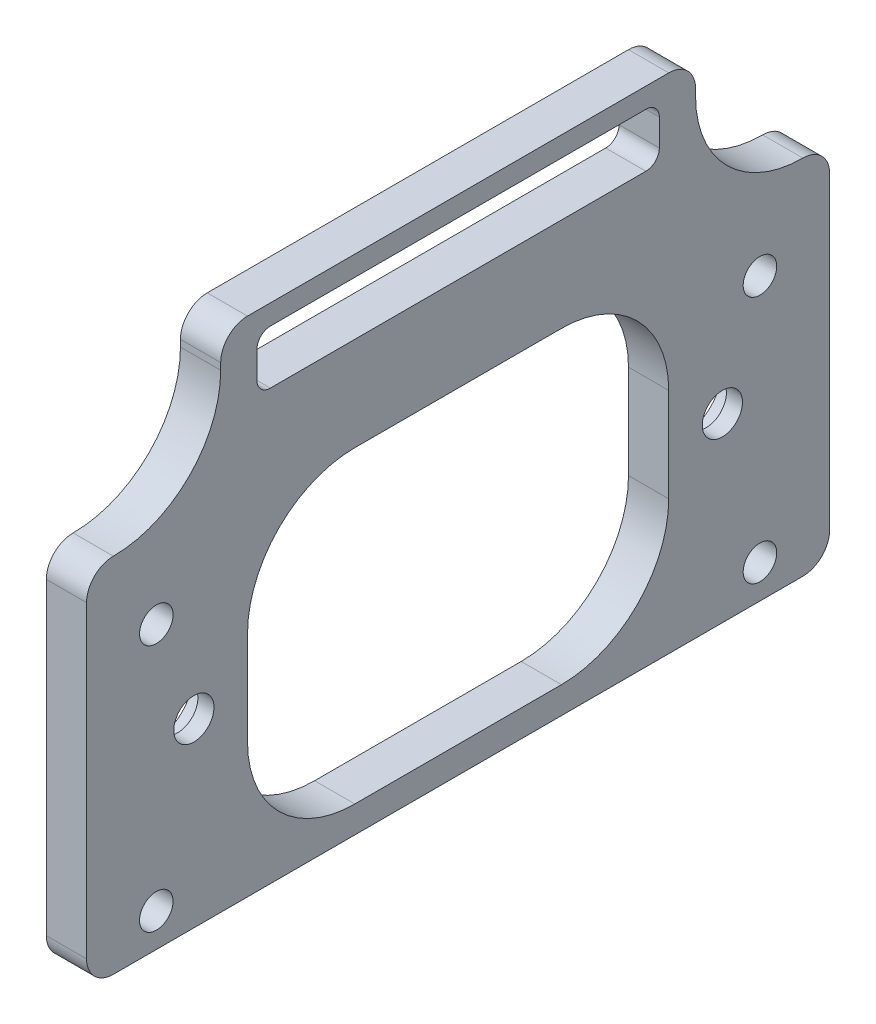
SolidWorks part; units mm, degrees
material "3.0205 (EN-AW 1200)"
ref_plane "前视基准面" through (0, 0, 0) normal (0, 0, 1) x (1, 0, 0)
ref_plane "上视基准面" through (0, 0, 0) normal (0, 1, 0) x (1, 0, 0)
ref_plane "右视基准面" through (0, 0, 0) normal (1, 0, 0) x (0, 0, -1)
other "Configuration Table"
sketch "草图1" plane through (0, 0, 0) normal (1, 0, 0) x (0, 0, -1)
  line L1 (0, 0) -> (55.4, 0)
  line L2 (0, 0) -> (0, 37.5)
  line L3 (0, 37.5) -> (55.4, 37.5)
  line L4 (55.4, 0) -> (55.4, 37.5)
  line L5 (12.7, 36) -> (42.7, 36)
  line L6 (12.7, 36) -> (12.7, 32)
  line L7 (12.7, 32) -> (42.7, 32)
  line L8 (42.7, 36) -> (42.7, 32)
  dimension "D1" = 55.4
  dimension "D2" = 37.5
  dimension "D3" = 1.5
  dimension "D4" = 12.7
  dimension "D5" = 30
  dimension "D6" = 4
extrude "凸台-拉伸1" add sketch "草图1" along normal blind 3
sketch "草图2" plane through (3, 0, 0) normal (1, 0, 0) x (0, 0, -1)
  line L0 (0, 37.5) -> (0, 0) construction
  line L1 (0, 0) -> (55.4, 0) construction
  circle A0 centre (5.2, 21) radius 1.25
  circle A1 centre (5.2, 2.5) radius 1.25
  circle A2 centre (50.2, 21) radius 1.25
  circle A3 centre (50.2, 2.5) radius 1.25
  dimension "D2" = 2.5
  dimension "D3" = 18.5
  dimension "D4" = 5.2
  dimension "D5" = 2.5
  dimension "D6" = 45
extrude "切除-拉伸1" cut sketch "草图2" against normal through all
sketch "草图3" plane through (3, 0, 0) normal (1, 0, 0) x (0, 0, -1)
  line L5 (0, 0) -> (55.4, 0) construction
  line L6 (27.7, 37.5) -> (27.7, 0) construction
  line L7 (0, 37.5) -> (10, 37.5)
  line L8 (0, 37.5) -> (0, 27)
  line L9 (0, 27) -> (10, 27)
  line L10 (10, 37.5) -> (10, 27)
  line L11 (55.4, 37.5) -> (0, 37.5) construction
  line L12 (55.4, 37.5) -> (45.4, 37.5)
  line L13 (55.4, 37.5) -> (55.4, 27)
  line L14 (55.4, 27) -> (45.4, 27)
  line L15 (45.4, 37.5) -> (45.4, 27)
  dimension "D5" = 10
  dimension "D6" = 10.5
extrude "切除-拉伸2" cut sketch "草图3" against normal through all
fillet "圆角2" radius 1 4 edges at (1.5, 36, -42.7) (1.5, 32, -42.7) (1.5, 36, -12.7) (1.5, 32, -12.7)
fillet "圆角3" radius 2 2 edges at (1.5, 37.5, -45.4) (1.5, 37.5, -10)
sketch "草图6" plane through (0, 0, 0) normal (-1, 0, 0) x (0, 0, 1)
  line L0 (-55.4, 0) -> (-55.4, 27) construction
  line L1 (0, 27) -> (0, 0) construction
  circle A0 centre (-47.4, 13.5) radius 1.5
  circle A1 centre (-8, 13.5) radius 1.5
  point P8 (-55.4, 13.5)
  dimension "D1" = 3
  dimension "D3" = 3
  dimension "D2" = 8
  dimension "D4" = 8
extrude "切除-拉伸4" cut sketch "草图6" against normal through all
sketch "草图7" plane through (0, 0, 0) normal (-1, 0, 0) x (0, 0, 1)
  circle A0 centre (-47.4, 13.5) radius 3
  circle A1 centre (-8, 13.5) radius 3
  dimension "D1" = 6
extrude "切除-拉伸5" cut sketch "草图7" against normal blind 1.8
fillet "圆角4" radius 8 2 edges at (1.5, 27, -45.4) (1.5, 27, -10)
sketch "草图10" plane through (0, 0, 0) normal (-1, 0, 0) x (0, 0, 1)
  line L0 (-55.4, 27) -> (0, 0) construction
  line L1 (0, 27) -> (-55.4, 0) construction
  line L2 (0, 27) -> (0, 0) construction
  line L3 (0, 0) -> (-55.4, 0) construction
  line L4 (-43.4, 2) -> (-12, 2)
  line L5 (-43.4, 2) -> (-43.4, 25)
  line L6 (-43.4, 25) -> (-12, 25)
  line L7 (-12, 2) -> (-12, 25)
  line L8 (-43.4, 2) -> (-12, 25) construction
  line L9 (-43.4, 25) -> (-12, 2) construction
  circle A0 centre (-8, 13.5) radius 3 construction
  point P9 (-27.7, 13.5)
  dimension "D2" = 4
  dimension "D1" = 2
extrude "切除-拉伸6" cut sketch "草图10" against normal blind 10
fillet "圆角5" radius 8 4 edges at (1.5, 2, -43.4) (1.5, 25, -43.4) (1.5, 2, -12) (1.5, 25, -12)
fillet "圆角6" radius 2 4 edges at (1.5, 27, -55.4) (1.5, 0, -55.4) (1.5, 0, 0) (1.5, 27, 0)
hole_wizard "M3 螺纹孔1" positions "3D草图2" profile "草图12" tap size "M3" standard "GB"
sketch3d "3D草图2"
  line L0 (0, 21, -50.2) -> (3, 21, -50.2) construction
  line L1 (0, 2.5, -50.2) -> (3, 2.5, -50.2) construction
  line L2 (0, 2.5, -5.2) -> (3, 2.5, -5.2) construction
  line L3 (0, 21, -5.2) -> (3, 21, -5.2) construction
  point P0 (0, 21, -50.2)
  point P4 (0, 2.5, -50.2)
  point P8 (0, 2.5, -5.2)
  point P12 (0, 21, -5.2)
sketch "草图12" plane through (0, 21, -50.2) normal (0, 1, 0) x (0, 0, 1)
  line L0 (0, 0) -> (0, 3.7511)
  line L1 (0, 3.7511) -> (1.25, 3)
  line L2 (1.25, 3) -> (1.25, 0)
  line L5 (1.25, 0) -> (0, 0)
  line L10 (0, 3.7511) -> (-1.25, 3) construction
  line L11 (0, -6.35) -> (0, 107.95) construction
  dimension "螺纹孔钻头直径" = 2.5
  dimension "螺纹孔钻头深度" = 3
  dimension "导头角度" = 118
cosmetic thread "孔螺纹线1" parameters "D1"=6, "D2"=3
cosmetic thread "孔螺纹线2" parameters "D1"=6, "D2"=3
cosmetic thread "孔螺纹线3" parameters "D1"=6, "D2"=3
cosmetic thread "孔螺纹线4" parameters "D1"=6, "D2"=3
